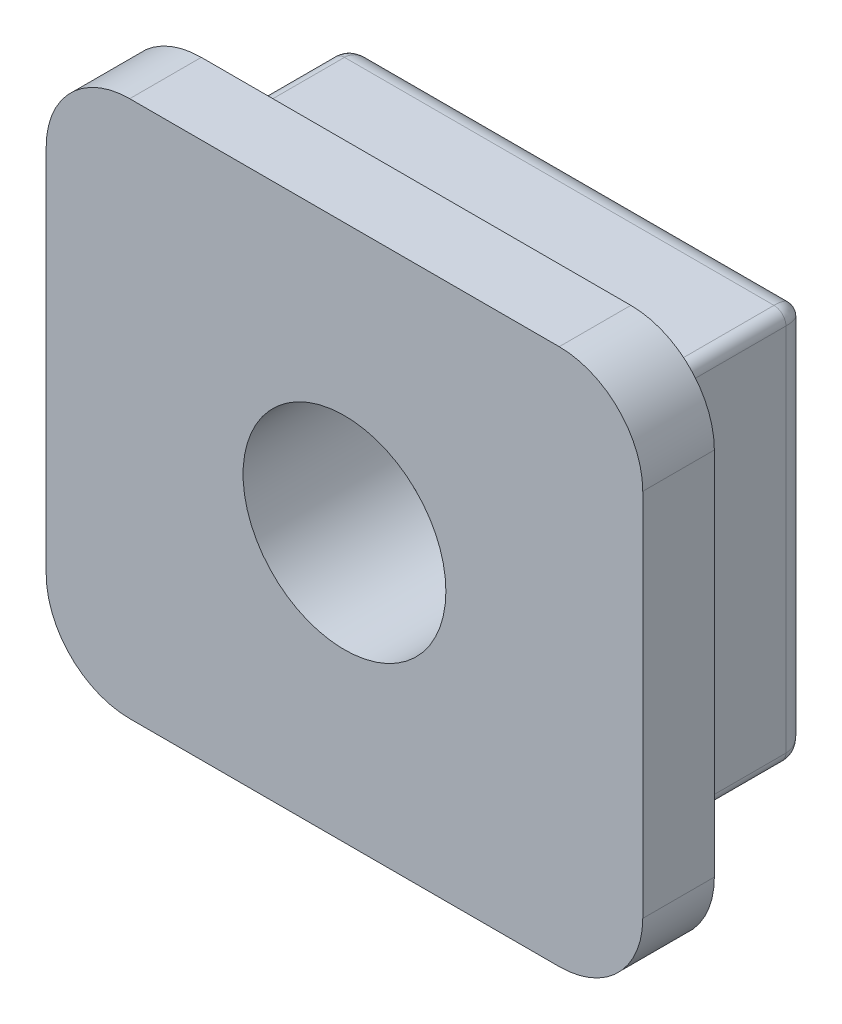
SolidWorks part; units mm, degrees
material "ABS"
ref_plane "Спереди" through (0, 0, 0) normal (0, 0, 1) x (1, 0, 0)
ref_plane "Сверху" through (0, 0, 0) normal (0, 1, 0) x (1, 0, 0)
ref_plane "Справа" through (0, 0, 0) normal (1, 0, 0) x (0, 0, -1)
sketch "Эскиз1" plane through (0, 0, 0) normal (0, 0, 1) x (1, 0, 0)
  line L8 (6.1954, 114.8923) -> (6.1954, 108.6923)
  line L9 (6.3954, 108.4923) -> (13.5954, 108.4923)
  line L10 (13.7954, 108.6923) -> (13.7954, 114.8923)
  line L11 (13.5954, 115.0923) -> (6.3954, 115.0923)
  line L12 (6.1954, 114.8923) -> (6.1954, 108.6923)
  line L13 (6.3954, 108.4923) -> (13.5954, 108.4923)
  line L14 (13.7954, 108.6923) -> (13.7954, 114.8923)
  line L15 (13.5954, 115.0923) -> (6.3954, 115.0923)
  arc A8 (6.3954, 115.0923) -> (6.1954, 114.8923) centre (6.3954, 114.8923) ccw
  arc A9 (6.1954, 108.6923) -> (6.3954, 108.4923) centre (6.3954, 108.6923) ccw
  arc A10 (13.5954, 108.4923) -> (13.7954, 108.6923) centre (13.5954, 108.6923) ccw
  arc A11 (13.7954, 114.8923) -> (13.5954, 115.0923) centre (13.5954, 114.8923) ccw
  arc A12 (6.3954, 115.0923) -> (6.1954, 114.8923) centre (6.3954, 114.8923) ccw
  arc A13 (6.1954, 108.6923) -> (6.3954, 108.4923) centre (6.3954, 108.6923) ccw
  arc A14 (13.5954, 108.4923) -> (13.7954, 108.6923) centre (13.5954, 108.6923) ccw
  arc A15 (13.7954, 114.8923) -> (13.5954, 115.0923) centre (13.5954, 114.8923) ccw
  dimension "D1" = 0.2
extrude "Кнопка" add sketch "Эскиз1" against normal blind 2.8
sketch "Эскиз2" plane through (0, 0, 0) normal (0, 0, 1) x (1, 0, 0)
  line L8 (4.9954, 114.8923) -> (4.9954, 108.6923)
  line L9 (6.3954, 107.2923) -> (13.5954, 107.2923)
  line L10 (14.9954, 108.6923) -> (14.9954, 114.8923)
  line L11 (13.5954, 116.2923) -> (6.3954, 116.2923)
  line L12 (4.9954, 114.8923) -> (4.9954, 108.6923)
  line L13 (6.3954, 107.2923) -> (13.5954, 107.2923)
  line L14 (14.9954, 108.6923) -> (14.9954, 114.8923)
  line L15 (13.5954, 116.2923) -> (6.3954, 116.2923)
  arc A8 (6.3954, 116.2923) -> (4.9954, 114.8923) centre (6.3954, 114.8923) ccw
  arc A9 (4.9954, 108.6923) -> (6.3954, 107.2923) centre (6.3954, 108.6923) ccw
  arc A10 (13.5954, 107.2923) -> (14.9954, 108.6923) centre (13.5954, 108.6923) ccw
  arc A11 (14.9954, 114.8923) -> (13.5954, 116.2923) centre (13.5954, 114.8923) ccw
  arc A12 (6.3954, 116.2923) -> (4.9954, 114.8923) centre (6.3954, 114.8923) ccw
  arc A13 (4.9954, 108.6923) -> (6.3954, 107.2923) centre (6.3954, 108.6923) ccw
  arc A14 (13.5954, 107.2923) -> (14.9954, 108.6923) centre (13.5954, 108.6923) ccw
  arc A15 (14.9954, 114.8923) -> (13.5954, 116.2923) centre (13.5954, 114.8923) ccw
  dimension "D1" = 1
extrude "Бортик" add sketch "Эскиз2" along normal blind 1.2
sketch "Эскиз3" plane through (0, 0, 1.2) normal (0, 0, 1) x (1, 0, 0)
  line L1 (-52.4, 113.4923) -> (-52.4, 110.0923) construction
  line L2 (-52.4, 113.4923) -> (-52.4, 110.0923) construction
  line L3 (-52.4, 113.4923) -> (14.9954, 113.4923) construction
  line L4 (14.9954, 108.6923) -> (14.9954, 114.8923) construction
  line L5 (-52.4, 110.0923) -> (14.9954, 110.0923) construction
  line L6 (-52.4, 111.7923) -> (14.9954, 111.7923) construction
  line L7 (9.9954, 116.2923) -> (9.9954, 107.2923) construction
  line L8 (13.5954, 116.2923) -> (6.3954, 116.2923) construction
  line L9 (6.3954, 107.2923) -> (13.5954, 107.2923) construction
  circle A0 centre (9.9954, 111.7923) radius 1.7
extrude "Отверстие под штырь кнопки" cut sketch "Эскиз3" against normal blind 2.4
fillet "Скругление1" radius 0.4 8 edges at (6.1954, 111.7923, -2.8) (6.2539, 108.5509, -2.8) (9.9954, 108.4923, -2.8) (13.7368, 108.5509, -2.8) (13.7954, 111.7923, -2.8) (13.7368, 115.0338, -2.8) (9.9954, 115.0923, -2.8) (6.2539, 115.0338, -2.8)
sketch "Эскиз иконки" plane through (0, 0, -2.8) normal (0, 0, -1) x (-1, 0, 0)
  line L0 (-9.9954, 114.6923) -> (-9.9954, 108.8923) construction
  line L1 (-6.5954, 114.6923) -> (-13.3954, 114.6923) construction
  line L2 (-13.3954, 108.8923) -> (-6.5954, 108.8923) construction
  line L3 (-13.3954, 111.7923) -> (-6.5954, 111.7923) construction
  line L4 (-13.3954, 114.6923) -> (-13.3954, 108.8923) construction
  line L5 (-6.5954, 108.8923) -> (-6.5954, 114.6923) construction
  line L7 (-12.4954, 112.1923) -> (-7.4954, 112.1923)
  line L8 (-12.4954, 112.1923) -> (-12.4954, 111.3923)
  line L9 (-12.4954, 111.3923) -> (-7.4954, 111.3923)
  line L10 (-7.4954, 112.1923) -> (-7.4954, 111.3923)
  line L11 (-9.9954, 111.3923) -> (-9.9954, 112.1923) construction
  line L12 (-12.4954, 111.7923) -> (-7.4954, 111.7923) construction
  line L20 (-12.4954, 114.6923) -> (-12.4954, 108.8923) construction
  line L21 (-7.4954, 114.6923) -> (-7.4954, 108.8923) construction
  line L23 (-12.4954, 113.7923) -> (-7.4954, 113.7923)
  line L24 (-12.4954, 113.7923) -> (-12.4954, 112.9923)
  line L25 (-12.4954, 112.9923) -> (-7.4954, 112.9923)
  line L26 (-7.4954, 113.7923) -> (-7.4954, 112.9923)
  line L27 (-12.4954, 110.5923) -> (-7.4954, 110.5923)
  line L28 (-12.4954, 110.5923) -> (-12.4954, 109.7923)
  line L29 (-12.4954, 109.7923) -> (-7.4954, 109.7923)
  line L30 (-7.4954, 110.5923) -> (-7.4954, 109.7923)
  point P12 (-9.9954, 111.7923)
  dimension "D1" = 0.8
  dimension "D2" = 5
  dimension "D3" = 0.8
  dimension "D4" = 0.8
